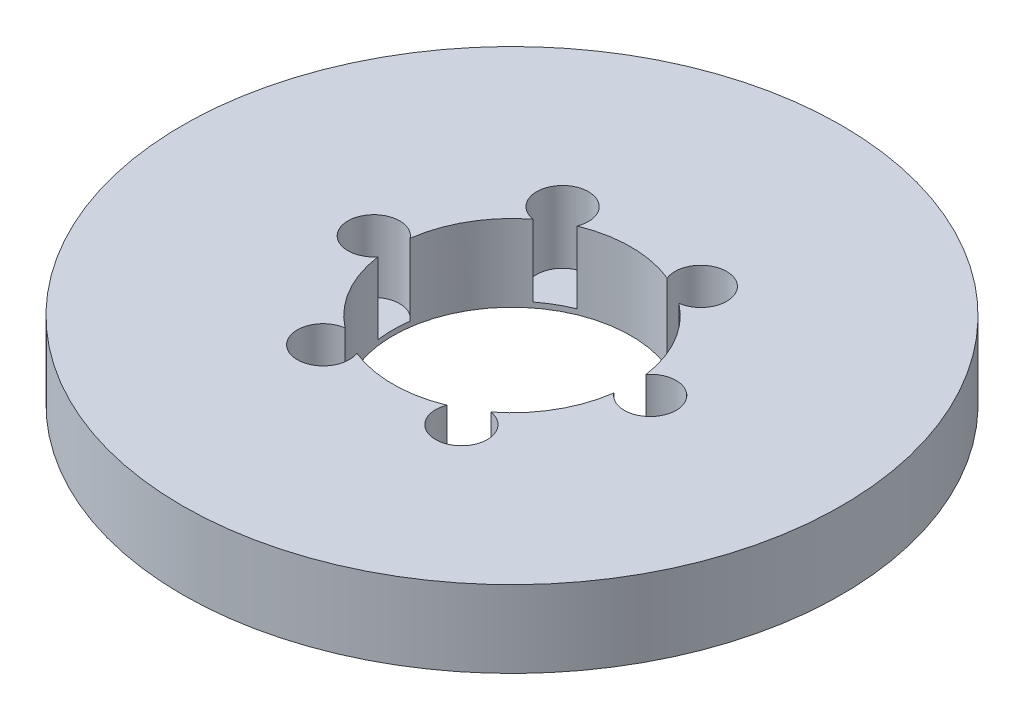
SolidWorks part; units mm, degrees
ref_plane "Front Plane" through (0, 0, 0) normal (0, 0, 1) x (1, 0, 0)
ref_plane "Top Plane" through (0, 0, 0) normal (0, 1, 0) x (1, 0, 0)
ref_plane "Right Plane" through (0, 0, 0) normal (1, 0, 0) x (0, 0, -1)
sketch "Sketch1" plane through (0, 0, 0) normal (0, 1, 0) x (1, 0, 0)
  circle A0 centre (0, 0) radius 90
  dimension "FLANGE_OD" = 180
extrude "Boss-Extrude1" add sketch "Sketch1" along normal blind 21
sketch "Sketch2" plane through (0, 0, 0) normal (0, 1, 0) x (1, 0, 0)
  circle A0 centre (0, 0) radius 32.5
  dimension "BORE_D" = 65
extrude "Cut-Extrude1" cut sketch "Sketch2" along normal through all
sketch "Sketch3" plane through (0, 21, 0) normal (0, 1, 0) x (1, 0, 0)
  circle A0 centre (0, 0) radius 37.7441 construction
  circle A1 centre (-37.7441, 0) radius 7.0753
  dimension "BOLT_D" = 14.1507
  dimension "BOLT_PCD" = 75.4883
extrude "Cut-Extrude2" cut sketch "Sketch3" against normal blind 19.5898
pattern_circular "CirPattern1" count 6 over 360 about axis through (0, 0, 0) along (0, 1, 0) of "Cut-Extrude2"
